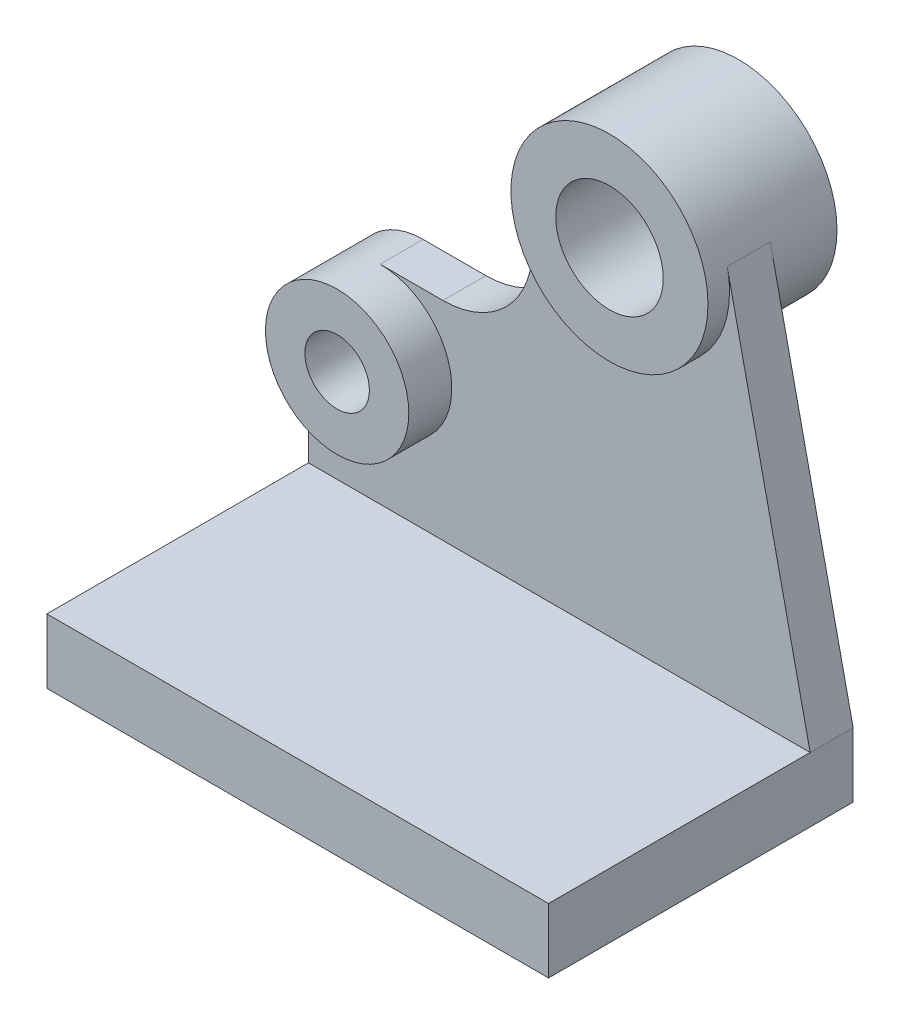
SolidWorks part; units mm, degrees
ref_plane "Front Plane" through (0, 0, 0) normal (0, 0, 1) x (1, 0, 0)
ref_plane "Top Plane" through (0, 0, 0) normal (0, 1, 0) x (1, 0, 0)
ref_plane "Right Plane" through (0, 0, 0) normal (1, 0, 0) x (0, 0, -1)
sketch "Sketch2" plane through (0, 0, 0) normal (0, 0, 1) x (1, 0, 0)
  line L0 (0, 0) -> (0, -100) construction
  line L1 (0, -100) -> (50, -100)
  line L2 (50, -100) -> (50, -118)
  line L3 (50, -118) -> (-90, -118)
  line L4 (-90, -118) -> (-90, -100)
  line L5 (-90, -100) -> (0, -100)
  line L6 (-70, -100) -> (-70, -62) construction
  line L7 (-90, -100) -> (-90, -62)
  line L8 (-70, -62) -> (-70, 0) construction
  line L9 (50, -100) -> (26.8661, 5.8705)
  line L10 (-70, -42) -> (-27.5, -42)
  line L11 (-27.5, -42) -> (-27.5, 0)
  circle A0 centre (0, 0) radius 27.5
  circle A1 centre (0, 0) radius 15
  circle A2 centre (-70, -62) radius 9
  circle A3 centre (-70, -62) radius 20
  dimension "D1" = 55
  dimension "D3" = 30
  dimension "D9" = 18
  dimension "D10" = 40
  dimension "D2" = 100
  dimension "D4" = 50
  dimension "D5" = 140
  dimension "D6" = 18
  dimension "D7" = 38
  dimension "D8" = 20
extrude "Boss-Extrude1" add sketch "Sketch2" along normal blind 12 contours A3 L7 L5 L1 L9 A0 L11 L10 region at (-9.9453, -66.1251, 0)
extrude "Boss-Extrude2" add sketch "Sketch2<3>" along normal blind 24 contours A3 A2 region at (-83.7421, -48.2579, 0)
sketch "Sketch2<3>" plane through (0, 0, 0) normal (0, 0, 1) x (1, 0, 0) same geometry as "Sketch2"
extrude "Boss-Extrude3" add sketch "Sketch2<4>" along normal mid plane 36 contours A0 A1 region at (26.5677, 2.8688, 0)
sketch "Sketch2<4>" plane through (0, 0, 0) normal (0, 0, 1) x (1, 0, 0) same geometry as "Sketch2"
extrude "Boss-Extrude4" add sketch "Sketch2<5>" along normal blind 85 contours L5 L4 L3 L2 L1 region at (-20, -109, 0)
sketch "Sketch2<5>" plane through (0, 0, 0) normal (0, 0, 1) x (1, 0, 0) same geometry as "Sketch2"
fillet "Fillet1" radius 25 1 edges at (-27.5, -42, 6)
